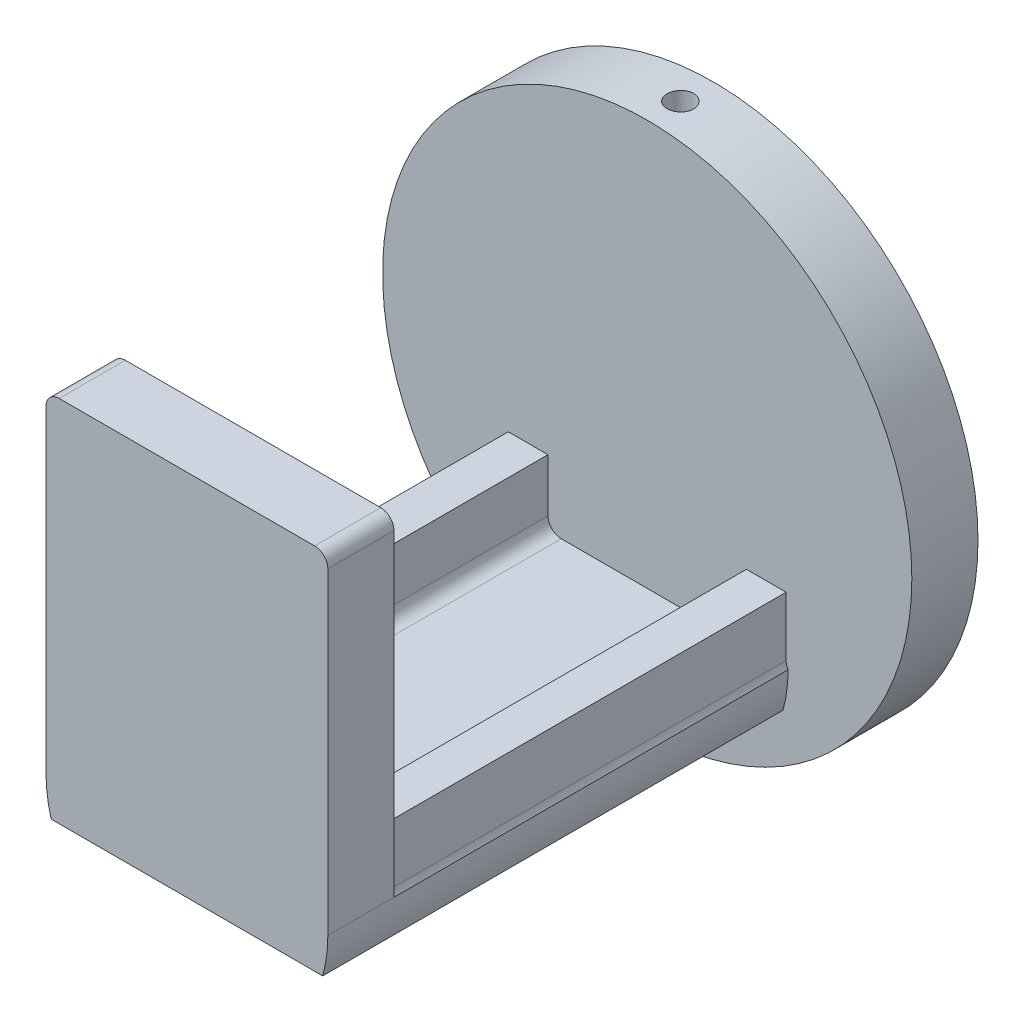
SolidWorks part; units mm, degrees
material "ABS"
ref_plane "Front Plane" through (0, 0, 0) normal (0, 0, 1) x (1, 0, 0)
ref_plane "Top Plane" through (0, 0, 0) normal (0, 1, 0) x (1, 0, 0)
ref_plane "Right Plane" through (0, 0, 0) normal (1, 0, 0) x (0, 0, -1)
sketch "Sketch1" plane through (0, 0, 0) normal (0, 0, 1) x (1, 0, 0)
  line L0 (-13.6056, -8.3607) -> (13.6056, -8.3607)
  line L1 (0, 20) -> (0, -11.3603) construction
  line L2 (-13.2709, -11.3603) -> (13.2709, -11.3603)
  circle A0 centre (0, 0) radius 20
  arc A1 (13.2709, -11.3603) -> (13.6056, -8.3607) centre (0, -8.3607) ccw
  arc A2 (-13.2709, -11.3603) -> (-13.6056, -8.3607) centre (0, -8.3607) cw
  point P5 (0, -8.3607)
  point P9 (0, -11.3603)
  dimension "D1" = 40
  dimension "D2" = 27.2113
  dimension "D3" = 26.5417
extrude "Boss-Extrude1" add sketch "Sketch1" against normal blind 5 contours A0
sketch "Sketch2" plane through (0, 0, 0) normal (0, 0, 1) x (1, 0, 0)
  line L0 (-10.65, -10.65) -> (10.65, -10.65)
  line L1 (0, 0) -> (0, -26.4743) construction
  line L2 (-10.2644, -13.49) -> (10.2644, -13.49)
  arc A0 (10.2644, -13.49) -> (10.65, -10.65) centre (0, -10.65) ccw
  arc A1 (-10.2644, -13.49) -> (-10.65, -10.65) centre (0, -10.65) cw
  point P5 (0, -10.65)
  point P8 (0, -13.49)
  dimension "D2" = 20.5287
  dimension "D3" = 10.65
  dimension "D1" = 21.3
  dimension "D4" = 10.65
extrude "Boss-Extrude2" add sketch "Sketch2" along normal blind 34.79
sketch "Sketch3" plane through (0, -10.65, 0) normal (0, 1, 0) x (1, 0, 0)
  line L0 (10.65, -29.79) -> (-10.65, -29.79)
  line L1 (10.65, -34.79) -> (10.65, 0) construction
  line L2 (-10.65, -34.79) -> (-10.65, 0) construction
  line L3 (-10.65, -29.79) -> (-10.65, -34.79)
  line L4 (-10.65, -34.79) -> (10.65, -34.79)
  line L5 (10.65, -34.79) -> (-10.65, -34.79) construction
  line L6 (10.65, -34.79) -> (10.65, -29.79)
  dimension "D1" = 5
extrude "Boss-Extrude3" add sketch "Sketch3" along normal blind 25
sketch "Sketch4" plane through (0, -10.65, 0) normal (0, 1, 0) x (1, 0, 0)
  line L0 (0, 0) -> (0, -34.79) construction
  line L1 (-10.65, -34.79) -> (10.65, -34.79) construction
  line L2 (7.5, 0) -> (7.5, -29.79)
  line L3 (10.65, 0) -> (-10.65, 0) construction
  line L4 (10.65, -29.79) -> (-10.65, -29.79) construction
  line L5 (7.5, -29.79) -> (10.5, -29.79)
  line L6 (10.5, -29.79) -> (10.5, 0)
  line L7 (10.5, 0) -> (7.5, 0)
  line L8 (-7.5, -29.79) -> (-10.5, -29.79)
  line L9 (-10.5, -29.79) -> (-10.5, 0)
  line L10 (-7.5, 0) -> (-7.5, -29.79)
  line L11 (-10.5, 0) -> (-7.5, 0)
  dimension "D1" = 7.5
  dimension "D2" = 3
extrude "Boss-Extrude5" add sketch "Sketch4" along normal blind 5
sketch "Sketch5" plane through (0, 0, 0) normal (0, 1, 0) x (1, 0, 0)
  line L0 (7.5, 0) -> (-7.5, 0) construction
  circle A0 centre (0, 2.5) radius 1
  dimension "D2" = 2
  dimension "D1" = 2.5
extrude "Cut-Extrude1" cut sketch "Sketch5" against normal through all and the other way blind 38 contours A0
fillet "Fillet1" radius 1 2 edges at (10.65, 14.35, 32.29) (-10.65, 14.35, 32.29)
fillet "Fillet2" radius 1 2 edges at (-7.5, -10.65, 14.895) (7.5, -10.65, 14.895)
fillet "Fillet3" radius 1 2 edges at (10.5, -10.65, 14.895) (-10.5, -10.65, 14.895)
sketch "Sketch6" plane through (0, 0, -5) normal (0, 0, -1) x (-1, 0, 0)
  line L0 (0, 20) -> (0, -20) construction
  line L1 (-20, 0) -> (20, 0) construction
  circle A0 centre (0, 0) radius 20 construction
  circle A1 centre (0, 11) radius 0.5
  circle A2 centre (0, -11) radius 0.5
  dimension "D1" = 1
  dimension "D2" = 11
extrude "Cut-Extrude2" cut sketch "Sketch6" against normal up to next
